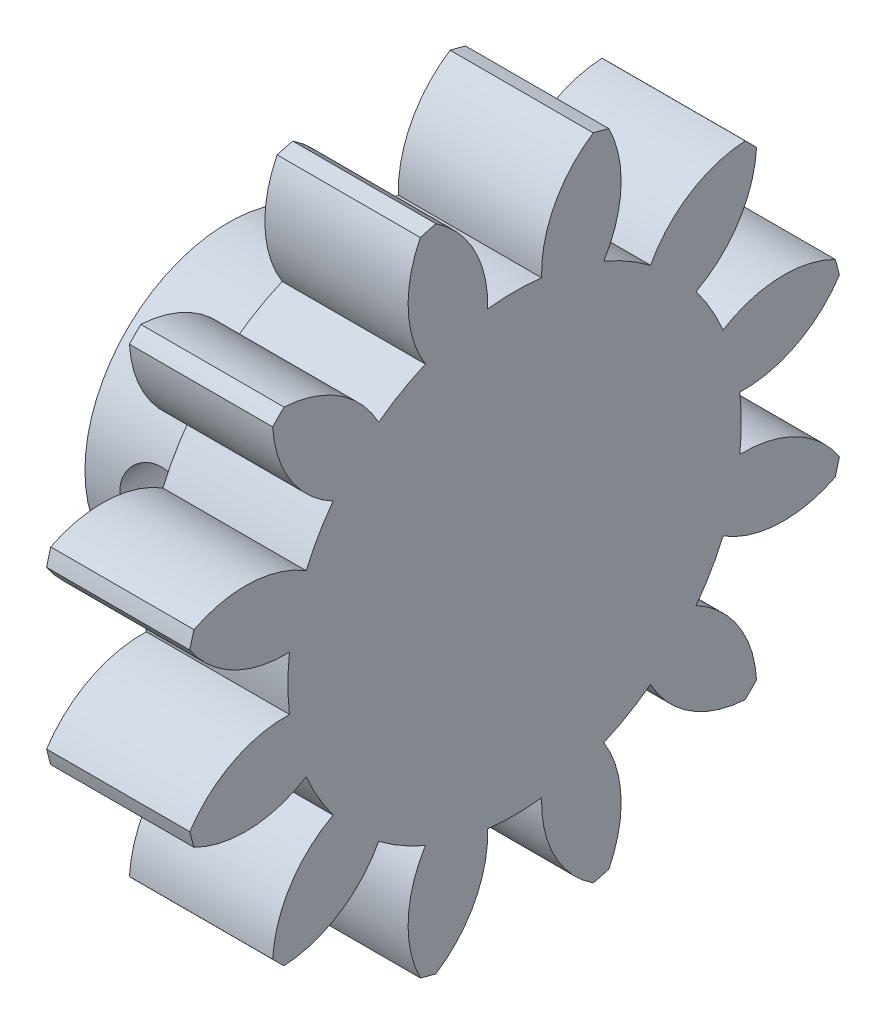
SolidWorks part; units mm, degrees
ref_plane "Plane1" through (0, 0, 0) normal (0, 0, 1) x (1, 0, 0)
ref_plane "Plane2" through (0, 0, 0) normal (0, 1, 0) x (1, 0, 0)
ref_plane "Plane3" through (0, 0, 0) normal (1, 0, 0) x (0, 0, -1)
other "Configuration Table"
sketch "HoldingSke" plane through (0, 0, 0) normal (0, 1, 0) x (1, 0, 0)
  line L0 (0, 0) -> (149.0697, -31.6857)
  line L1 (-15, 0) -> (100, 0) construction
  line L2 (0, 0) -> (-2.1039, 2.3779)
  line L3 (0, 0) -> (-11.863, 4.5341)
  line L4 (0, 0) -> (8.4473, 1.7955)
  line L5 (0, 0) -> (-47.5972, -17.7524)
  line L6 (0, 0) -> (-10.5278, -7.1032)
  line L7 (-2.1039, 2.3779) -> (8.831, 51.9882)
  line L8 (-76.2, 54.61) -> (-54.9402, 54.61)
  line L9 (-71.009, 38.7566) -> (-53.1078, 45.2721)
  line L10 (-76.2, 71.12) -> (104.1128, 71.12)
  line L11 (0, 0) -> (-12.7, 0)
  line L12 (-76.2, 101.6) -> (-76.0298, 101.6)
  line L13 (24.9733, 27.94) -> (52.9518, 28.4284)
  line L14 (24.9733, 27.94) -> (24.9746, 27.94)
  line L15 (24.9733, 27.94) -> (100.4006, 29.5858)
  circle A0 centre (0, 0) radius 9.525
  circle A1 centre (0, 0) radius 20.1071
  circle A2 centre (0, 0) radius 38.1
  circle A3 centre (0, 0) radius 9.525
  dimension "MHD" = 40.2141
  dimension "Hub_dia" = 76.2
  dimension "Bore" = 19.05
  dimension "MBD" = 19.05
  dimension "Num_teeth" = 12
  dimension "Pitch" = 152.4
  dimension "Overall_len" = 50.8
  dimension "Show_teeth" = 12
  dimension "Thickness" = 12.7
  dimension "OAL" = 50.8011
  dimension "T_dim" = 21.2598
  dimension "Ap" = 20
  dimension "H" = 19.05
  dimension "Pitch_radius" = 180.3128
  dimension "Width" = 12.7
  dimension "Backlash" = 0.1702
  dimension "Addendum_fac" = 1
  dimension "Dedendum_fac" = 1.25
  dimension "Clearance_fac" = 0.25
  dimension "Dedendum_add" = 0.0013
sketch "BasProSke" plane through (0, 0, 0) normal (0, 1, 0) x (1, 0, 0)
  line L0 (-10, 0) -> (60, 0) construction
  line L1 (0, 0) -> (0, 29.6333)
  line L2 (0, 0) -> (12.7, 0)
  line L3 (12.7, 0) -> (12.7, 29.6333)
  line L4 (12.7, 29.6333) -> (0, 29.6333)
  dimension "Thickness" = 12.7
  dimension "Diameter" = 59.2667
revolve "Base-Revolve" add sketch "BasProSke" angle 360 about L0
sketch "TooCutSke" plane through (0, 0, 0) normal (1, 0, 0) x (0, 0, -1)
  line L1 (0, 0) -> (0, 107) construction
  line L2 (0, 0) -> (-3.6127, 25.1418) construction
  line L3 (0, 0) -> (-13.0549, 48.7215) construction
  line L4 (-3.6127, 25.1418) -> (-6.5274, 24.3608) construction
  arc A0 (2.3928, 19.9642) -> (-2.3928, 19.9642) centre (0, 0) ccw
  arc A1 (7.0051, 28.8196) -> (-7.0051, 28.8196) centre (0, 0) ccw
  circle A2 centre (0, 0) radius 25.4 construction
  circle A3 centre (0, 0) radius 23.8682 construction
  arc A4 (-2.3928, 19.9642) -> (-7.0051, 28.8196) centre (-12.5471, 20.3042) ccw
  arc A5 (7.0051, 28.8196) -> (2.3928, 19.9642) centre (12.5471, 20.3042) ccw
  dimension "Root_dia" = 40.2141
  dimension "Overcut_dia" = 59.3175
  dimension "Pitch_dia" = 50.8
  dimension "Base_dia" = 47.7364
  dimension "Flank_rad" = 10.16
  dimension "Half_ang" = 15
  dimension "Half_CT" = 3.0176
extrude "ToothCut" cut sketch "TooCutSke" along normal through all
fillet "Breaks" [suppressed] radius 0.0847 tangent propagation no
fillet "RootFillets" [suppressed] radius 1.0596
pattern_circular "TeethCuts" count 12 every 30 about axis through (-10, 0, 0) along (1, 0, 0) of "ToothCut", "RootFillets", "Breaks"
sketch "HubNeaOneSke" plane through (0, 0, 0) normal (-1, 0, 0) x (0, 0, 1)
  circle A0 centre (0, 0) radius 20.1071
  dimension "Diameter" = 40.2141
extrude "HubNearOne" [suppressed] add sketch "HubNeaOneSke" along normal blind 38.1011
sketch "HubNeaBotSke" plane through (0, 0, 0) normal (-1, 0, 0) x (0, 0, 1)
  circle A0 centre (0, 0) radius 20.1071
  dimension "Diameter" = 40.2141
extrude "HubNearBoth" [suppressed] add sketch "HubNeaBotSke" along normal blind 19.0506
ref_plane "FarPln" through (12.7, 0, 0) normal (1, 0, 0) x (0, 0, -1)
sketch "HubFarSke" plane through (12.7, 0, 0) normal (1, 0, 0) x (0, 0, -1)
  circle A0 centre (0, 0) radius 20.1071
  dimension "Diameter" = 40.2141
extrude "HubFar" [suppressed] add sketch "HubFarSke" along normal blind 19.0506
sketch "Sketch1" plane through (0, 0, 0) normal (-1, 0, 0) x (0, 0, 1)
  circle A0 centre (0, 0) radius 12.7
  circle A1 centre (0, 0) radius 5.715
  dimension "D1" = 25.4
  dimension "D2" = 11.43
extrude "Boss-Extrude1" add sketch "Sketch1" along normal blind 12.7
ref_plane "Plane4" through (0, 0, 13.97) normal (0, 0, 1) x (1, 0, 0)
sketch "Sketch2" plane through (0, 0, 13.97) normal (0, 0, 1) x (1, 0, 0)
  line L0 (0, 2.3928) -> (0, -2.3928) construction
  line L1 (0, 0) -> (-11.6247, 0) construction
  circle A0 centre (-6.35, 0) radius 3.2512
  dimension "D2" = 6.5024
  dimension "D1" = 6.35
extrude "Cut-Extrude1" cut sketch "Sketch2" against normal up to surface (8.255 mm away) up to face at (-12.7, 0, 5.715)
sketch "Sketch4" plane through (0, 0, 0) normal (0, 0, 1) x (1, 0, 0)
  line L0 (0, 2.3928) -> (0, -2.3928) construction
  line L1 (-1.524, 2.7863) -> (-6.35, 5.5726)
  line L2 (-6.35, 5.5726) -> (-11.176, 2.7863)
  line L3 (-11.176, 2.7863) -> (-11.176, -2.7863)
  line L4 (-11.176, -2.7863) -> (-6.35, -5.5726)
  line L5 (-6.35, -5.5726) -> (-1.524, -2.7863)
  line L6 (-1.524, -2.7863) -> (-1.524, 2.7863)
  circle A0 centre (-6.35, 0) radius 4.826 construction
  dimension "D1" = 9.652
extrude "Cut-Extrude2" cut sketch "Sketch4" along normal blind 7.62
equation "' \"Pitch@HoldingSke\" = 4"
equation "' \"Num_teeth@HoldingSke\" = 12"
equation "' \"Ap@HoldingSke\" =  20"
equation "' \"Ap@HoldingSke\" = 20"
equation "' \"Width@HoldingSke\" = 0.5"
equation "' \"Hub_dia@HoldingSke\"= 1"
equation "' \"Hub_dia@HoldingSke\" = 1"
equation "' \"Overall_len@HoldingSke\" = 1.0"
equation "' \"Bore@HoldingSke\" = 0.75"
equation "' \"T_dim@HoldingSke\" = 0.85"
equation "' \"Width@KeySke\" = 0.25"
equation "' \"Show_teeth@HoldingSke\" = 13"
equation "' \"Backlash@HoldingSke\" = 0.009"
equation "' \"Addendum_fac@HoldingSke\" = 1.0"
equation "' \"Dedendum_fac@HoldingSke\" = 1.25"
equation "' \"Dedendum_add@HoldingSke\" = 0.00005"
equation "' \"Clearance_fac@HoldingSke\" = 0.25"
equation "' \"Pitch@HoldingSke\" = 0.5"
equation "' \"Num_teeth@HoldingSke\" = 23"
equation "' \"Show_teeth@HoldingSke\" = 23"
equation "' \"Backlash@HoldingSke\" = 0.0375"
equation "\"Overcut_dia@TooCutSke\" = (\"Num_teeth@HoldingSke\" + 2 * \"Addendum_fac@HoldingSke\") / \"Pitch@HoldingSke\" + 0.002"
equation "\"Pitch_dia@TooCutSke\" = \"Num_teeth@HoldingSke\" / \"Pitch@HoldingSke\""
equation "\"Base_dia@TooCutSke\" = \"Num_teeth@HoldingSke\" / \"Pitch@HoldingSke\" * cos((\"Ap@HoldingSke\"  * 3.14159265 / 180))"
equation "\"Root_dia@TooCutSke\" = (\"Num_teeth@HoldingSke\" + 2) / \"Pitch@HoldingSke\" - 2 * (\"Addendum_fac@HoldingSke\" + \"Dedendum_fac@HoldingSke\") / \"Pitch@HoldingSke\" - \"Dedendum_add@HoldingSke\" * 2"
equation "\"Half_ang@TooCutSke\" = 180 / \"Num_teeth@HoldingSke\""
equation "\"Half_CT@TooCutSke\" = \"Num_teeth@HoldingSke\" / \"Pitch@HoldingSke\" * sin((3.14159265 / 2 / \"Num_teeth@HoldingSke\")) / 2 - 7 * \"Backlash@HoldingSke\" / 4"
equation "\"Flank_rad@TooCutSke\" = \"Num_teeth@HoldingSke\" / \"Pitch@HoldingSke\" / 5"
equation "\"Radius@RootFillets\" = \"Clearance_fac@HoldingSke\" / \"Pitch@HoldingSke\" + \"Dedendum_add@HoldingSke\""
equation "\"Break_rad@Breaks\" = 0.02 / \"Pitch@HoldingSke\""
equation "\"Thickness@HoldingSke\" = \"Width@HoldingSke\""
equation "\"OAL@HoldingSke\" = \"Thickness@HoldingSke\""
equation "\"MHD@HoldingSke\" = (\"Num_teeth@HoldingSke\" + 2) / \"Pitch@HoldingSke\" - 2 * (\"Addendum_fac@HoldingSke\" + \"Dedendum_fac@HoldingSke\")  / \"Pitch@HoldingSke\" - \"Dedendum_add@HoldingSke\" * 2"
equation "\"MBD@HoldingSke\" = (\"Num_teeth@HoldingSke\" + 2) / \"Pitch@HoldingSke\" - 2 * (\"Addendum_fac@HoldingSke\" + \"Dedendum_fac@HoldingSke\")  / \"Pitch@HoldingSke\" - \"Dedendum_add@HoldingSke\" * 2 - 0.002"
equation "\"MHD@HoldingSke\" = ((sgn( \"MHD@HoldingSke\" - \"Hub_dia@HoldingSke\" )-1)*( \"MHD@HoldingSke\" - \"Hub_dia@HoldingSke\" ))/-2+ \"Hub_dia@HoldingSke\""
equation "\"MBD@HoldingSke\" = ((sgn( \"MBD@HoldingSke\" - \"Bore@HoldingSke\" )-1)*( \"MBD@HoldingSke\" - \"Bore@HoldingSke\" ))/-2+ \"Bore@HoldingSke\""
equation "\"OAL@HoldingSke\" = ((sgn( \"OAL@HoldingSke\" - \"Overall_len@HoldingSke\" )+1)*( \"OAL@HoldingSke\" - \"Overall_len@HoldingSke\" ))/2 + \"Overall_len@HoldingSke\" + 0.000002"
equation "\"Num_teeth@TeethCuts\" = int( \"Show_teeth@HoldingSke\" ) + 1"
equation "\"Num_teeth@TeethCuts\" = ((sgn( \"Num_teeth@TeethCuts\" - \"Num_teeth@HoldingSke\" )-1)*( \"Num_teeth@TeethCuts\" - \"Num_teeth@HoldingSke\" ))/-2+ \"Num_teeth@HoldingSke\""
equation "\"Num_teeth@TeethCuts\" = ((sgn( \"Num_teeth@TeethCuts\" - 2.0)+1)*( \"Num_teeth@TeethCuts\" - 2.0))/2 +2.0"
equation "\"Angle@TeethCuts\" = 360.0 / \"Num_teeth@HoldingSke\""
equation "\"Diameter@BasProSke\" = (\"Num_teeth@HoldingSke\" + 2 * \"Addendum_fac@HoldingSke\") / \"Pitch@HoldingSke\""
equation "\"Thickness@BasProSke\"  = \"Thickness@HoldingSke\""
equation "' \"Fillet_rad@BasProSke\" =  \"Thickness@HoldingSke\" * 0.05"
equation "' \"Fillet_rad@BasProSke\" = \"Thickness@HoldingSke\" * 0.05"
equation "\"MHD@HoldingSke\" = ((sgn( \"MHD@HoldingSke\" - \"Root_dia@TooCutSke\" )-1)*( \"MHD@HoldingSke\" - \"Root_dia@TooCutSke\" ))/-2+ \"Root_dia@TooCutSke\""
equation "\"Diameter@HubNeaOneSke\" = \"MHD@HoldingSke\""
equation "\"Length@HubNearOne\" = \"OAL@HoldingSke\" - \"Thickness@BasProSke\""
equation "\"Diameter@HubNeaBotSke\" = \"MHD@HoldingSke\""
equation "\"Length@HubNearBoth\" = ( \"OAL@HoldingSke\" - \"Thickness@BasProSke\" ) / 2.0"
equation "\"Thickness@FarPln\" = \"Thickness@BasProSke\""
equation "\"Diameter@HubFarSke\" = \"MHD@HoldingSke\""
equation "\"Length@HubFar\" = ( \"OAL@HoldingSke\" - \"Thickness@BasProSke\" ) / 2.0"
equation "\"Diameter@BorSke\" = \"MBD@HoldingSke\""
equation "\"D1@Bore\" = \"OAL@HoldingSke\" * 2.0"
equation "\"D1@Keyway\" = \"OAL@HoldingSke\" * 2.0"
equation "\"Offset@KeySke\" = \"T_dim@HoldingSke\" - \"MBD@HoldingSke\" / 2.0"
